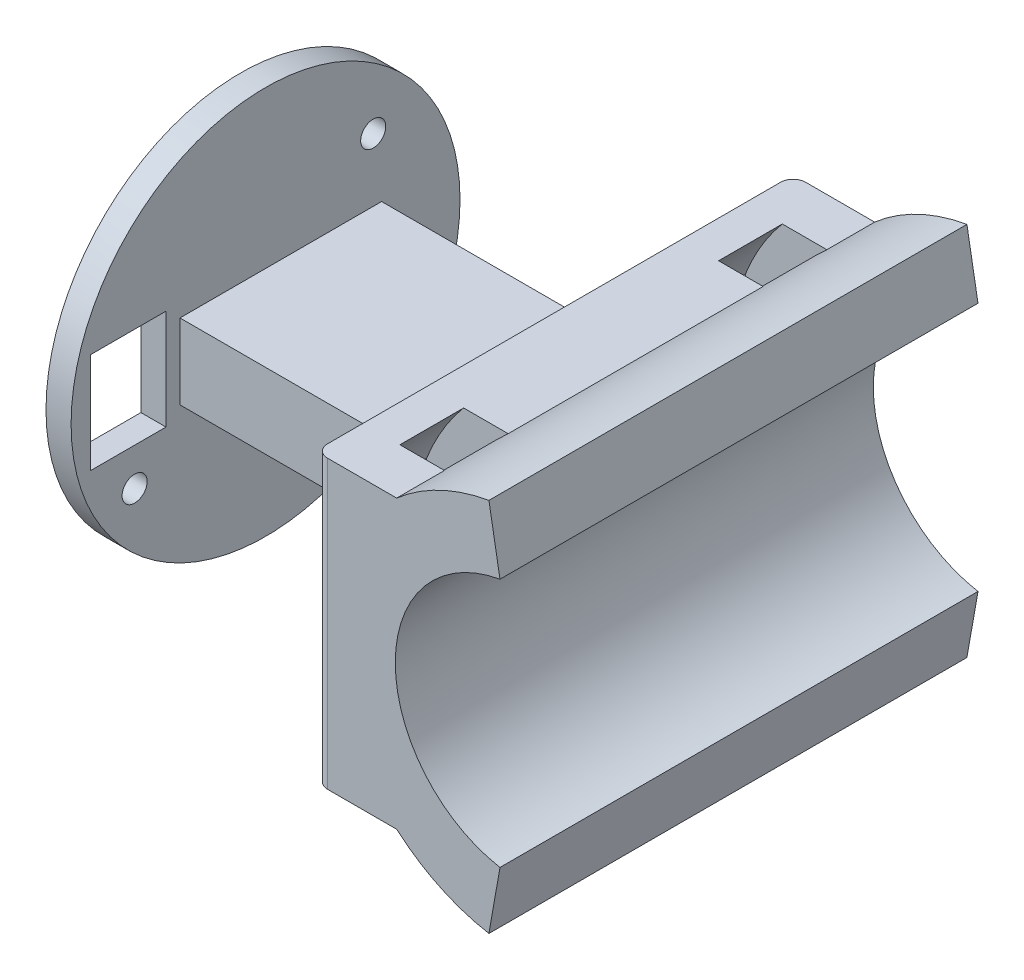
SolidWorks part; units mm, degrees
ref_plane "Top Plane" through (0, 0, 0) normal (0, 0, 1) x (1, 0, 0)
ref_plane "Right Plane" through (0, 0, 0) normal (0, 1, 0) x (1, 0, 0)
ref_plane "Front Plane" through (0, 0, 0) normal (1, 0, 0) x (0, 0, -1)
ref_axis "x-axis" through (-88.99, 0, 0) along (1, 0, 0)
ref_axis "y-axis" through (0, -55, 0) along (0, 1, 0)
ref_axis "z-axis" through (0, 0, 55) along (0, 0, -1)
sketch "Sketch1" plane through (0, 0, 0) normal (0, 0, 1) x (1, 0, 0)
  line L0 (8.3462, -9.9466) -> (7.464, -14.9494)
  line L2 (8.3462, -9.9466) -> (10.1, 0) construction
  line L4 (10.1, 0) -> (8.3462, 9.9466) construction
  line L5 (8.3462, 9.9466) -> (7.464, 14.9494)
  line L6 (20.955, 0) -> (-20.955, 0) construction
  line L7 (8.3462, -9.9466) -> (8.3462, 9.9466) construction
  line L8 (0, 0) -> (-6.3894, 0) construction
  line L11 (0.1106, 11.43) -> (-6.3894, 11.43)
  line L12 (-6.3894, -11.43) -> (-6.3894, 11.43)
  line L13 (0.1106, -11.43) -> (-6.3894, -11.43) construction
  line L22 (0.1106, -11.43) -> (-6.3894, -11.43)
  arc A0 (8.3462, -9.9466) -> (8.3462, 9.9466) centre (10.1, 0) cw
  arc A1 (7.464, -14.9494) -> (0.1106, -11.43) centre (10.1, 0) cw
  arc A2 (0.1106, 11.43) -> (7.464, 14.9494) centre (10.1, 0) cw
  dimension "D1" = 160
  dimension "D2" = 5.08
  dimension "D3" = 10.1
  dimension "D4" = 6.5
  dimension "D5" = 22.86
extrude "Boss-Extrude1" add sketch "Sketch1" along normal mid plane 38.1
ref_axis "Axis2" through (10.1, 0, 19.05) along (0, 0, -1)
sketch "Sketch6" plane through (-6.3894, 0, 0) normal (-1, 0, 0) x (0, 0, 1)
  line L12 (-9.2494, -3) -> (6.822, -3)
  line L13 (-9.2494, -3) -> (-9.2494, 3)
  line L14 (-9.2494, 3) -> (6.822, 3)
  line L15 (6.822, -3) -> (6.822, 3)
  line L16 (-4.7767, 0) -> (-4.7767, -3) construction
  line L17 (19.05, 0) -> (-19.05, 0) construction
  line L18 (-2.6665, 0) -> (-2.6665, 3) construction
  dimension "D1" = 6
extrude "Boss-Extrude3" add sketch "Sketch6" along normal blind 23
sketch "Sketch3" plane through (0, 0, 0) normal (0, 1, 0) x (1, 0, 0)
  line L0 (0, -12.7) -> (0, 12.7) construction
  line L1 (-5.08, 12.7) -> (0, 12.7) construction
  line L2 (-7.62, 15.24) -> (-5.08, 15.24)
  line L3 (-7.62, 15.24) -> (-7.62, 10.16)
  line L4 (-7.62, 10.16) -> (-5.08, 10.16)
  line L5 (-5.08, 15.24) -> (-5.08, 10.16)
  line L6 (-7.62, 15.24) -> (-5.08, 15.24)
  line L7 (-7.62, 10.16) -> (-5.08, 10.16)
  line L8 (-6.3885, 0) -> (6.3885, 0) construction
  line L9 (-5.08, -12.7) -> (0, -12.7) construction
  line L10 (-5.08, -15.24) -> (-5.08, -10.16)
  line L11 (-7.62, -10.16) -> (-5.08, -10.16)
  line L12 (-7.62, -15.24) -> (-7.62, -10.16)
  line L13 (-7.62, -15.24) -> (-5.08, -15.24)
  point P4 (0, 0)
  dimension "D1" = 5.08
  dimension "D2" = 2.54
  dimension "D3" = 5.08
  dimension "D4" = 25.4
revolve "Cut-Revolve1" cut sketch "Sketch3" angle 360 about axis through (10.1, 0, 19.05) along (0, 0, -1) region at (-6.35, 0, -12.7) region at (-6.35, 0, 12.7)
sketch "Sketch5" plane through (-6.3894, 0, 0) normal (-1, 0, 0) x (0, -1, 0)
  line L0 (11.43, 19.05) -> (11.43, -19.05) construction
  line L1 (-11.43, 19.05) -> (11.43, 19.05)
  line L2 (-11.43, 19.05) -> (-11.43, -5.3894)
  line L3 (-11.43, -5.3894) -> (11.43, -5.3894)
  line L4 (11.43, 19.05) -> (11.43, -5.3894)
sketch "Sketch4" plane through (-29.3894, 0, 0) normal (-1, 0, 0) x (0, -1, 0)
  line L0 (0, 19.05) -> (0, -19.05) construction
  line L5 (-4, 7.9307) -> (0, 7.9307) construction
  line L6 (0, 7.0768) -> (4, 7.0768) construction
  line L7 (0, -14) -> (0, -15.5) construction
  line L8 (-0.0257, 13.9362) -> (-0.0257, 15.4362) construction
  line L9 (-4.0257, 13.9362) -> (3.9743, 13.9362)
  line L10 (-4.0257, 13.9362) -> (-4.0257, 7.9362)
  line L11 (-4.0257, 7.9362) -> (3.9743, 7.9362)
  line L12 (3.9743, 13.9362) -> (3.9743, 7.9362)
  line L13 (-4.0257, 9.9362) -> (-7.0257, 9.9362) construction
  line L14 (6.9743, 10.436) -> (3.9743, 10.436) construction
  circle A0 centre (0, 0) radius 15.5
  circle A3 centre (6.9743, 10.436) radius 1
  circle A5 centre (-8.0257, -8.5809) radius 1
  dimension "D1" = 31
  dimension "D5" = 2
  dimension "D6" = 2
  dimension "D2" = 2
  dimension "D3" = 2.4998
  dimension "D4" = 1.5
extrude "Boss-Extrude2" add sketch "Sketch4" along normal blind 2
fillet "Fillet1" radius 1 2 edges at (-6.3894, 0, -19.05) (-6.3894, 0, 19.05)
